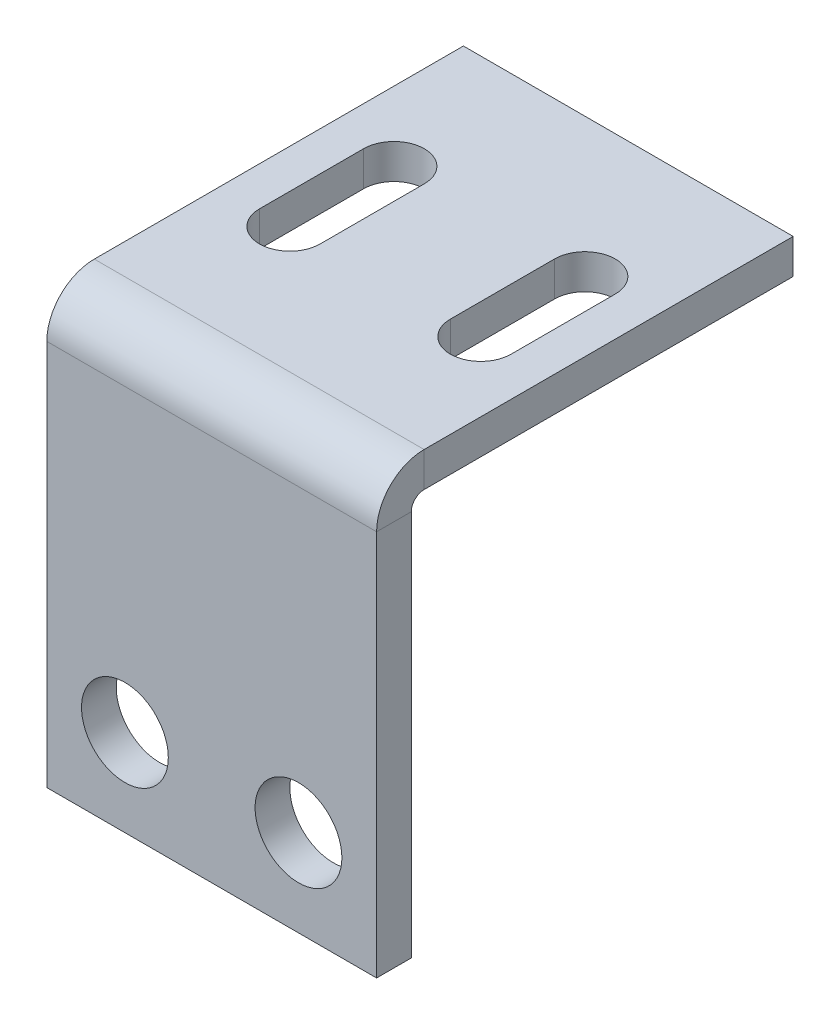
SolidWorks part; units mm, degrees
note: The reader was unsure of these and kept them because the rebuilt part matched: flange length of "边线-法兰1".
ref_plane "前视基准面" through (0, 0, 0) normal (0, 0, 1) x (1, 0, 0)
ref_plane "上视基准面" through (0, 0, 0) normal (0, 1, 0) x (1, 0, 0)
ref_plane "右视基准面" through (0, 0, 0) normal (1, 0, 0) x (0, 0, -1)
sketch "草图1" plane through (0, 0, 0) normal (0, 0, 1) x (1, 0, 0)
  line L1 (-9.5, 12.5) -> (9.5, 12.5)
  line L2 (-9.5, 12.5) -> (-9.5, -12.5)
  line L3 (-9.5, -12.5) -> (9.5, -12.5)
  line L4 (9.5, 12.5) -> (9.5, -12.5)
  line L5 (-9.5, 12.5) -> (9.5, -12.5) construction
  line L6 (-9.5, -12.5) -> (9.5, 12.5) construction
  circle A0 centre (-5, -7.5) radius 2.5
  circle A1 centre (5, -7.5) radius 2.5
  point P0 (0, 0)
  dimension "D3" = 5
  dimension "D1" = 19
  dimension "D2" = 25
  dimension "D4" = 5
  dimension "D5" = 4.5
  dimension "D6" = 10
sheet metal parameters "钣金1" thickness 2 parameters "D1"=0.7366
base flange "基体-法兰1" sketch "草图1" thickness 2 reverse thickness direction no parameters "D1"=0.7366
edge flange "边线-法兰1" sketch "草图5" flange angle 90 flange length 22 flange position material inside bend radius 0.7366 thickness 2 relief rectangular parameters "D6"=10
sketch "草图5" plane through (0, 12.5, -2) normal (0, 1, 0) x (1, 0, 0)
  line L2 (-9.5, 0) -> (-9.5, 22)
  line L3 (-9.5, 22) -> (9.5, 22)
  line L4 (9.5, 22) -> (9.5, 0)
  line L5 (9.5, 0) -> (-9.5, 0) construction
  line L6 (9.5, 0) -> (-9.5, 0)
bend "边线折弯1" bend radius 0.7366 bend angle 90 parameters "D5"=1
sketch "草图6" plane through (0, 12.5, 0) normal (0, 1, 0) x (1, 0, 0)
  line L0 (-5.5, 10) -> (-5.5, 16) construction
  line L1 (-7.25, 10) -> (-7.25, 16)
  line L2 (-3.75, 10) -> (-3.75, 16)
  line L3 (5.5, 10) -> (5.5, 16) construction
  line L4 (3.75, 10) -> (3.75, 16)
  line L5 (7.25, 10) -> (7.25, 16)
  line L6 (-9.5, 24) -> (-9.5, 2.7366) construction
  line L7 (9.5, 0) -> (-9.5, 0) construction
  arc A0 (-7.25, 10) -> (-3.75, 10) centre (-5.5, 10) ccw
  arc A1 (-3.75, 16) -> (-7.25, 16) centre (-5.5, 16) ccw
  arc A2 (3.75, 10) -> (7.25, 10) centre (5.5, 10) ccw
  arc A3 (7.25, 16) -> (3.75, 16) centre (5.5, 16) ccw
  point P2 (-5.5, 13)
  point P7 (5.5, 13)
  dimension "D1" = 4
  dimension "D2" = 11
  dimension "D3" = 3.5
  dimension "D4" = 16
  dimension "D5" = 6
  dimension "D6" = 16
  dimension "D7" = 6
extrude "切除-拉伸1" cut sketch "草图6" against normal blind 10 normal cut yes
flat pattern "平板型式1" [suppressed]
sketch "折弯-线1" plane through (0, 0, 0) normal (0, 1, 0) x (-1, 0, 0)
bend of the flat pattern "展开-<边线折弯1>1"
